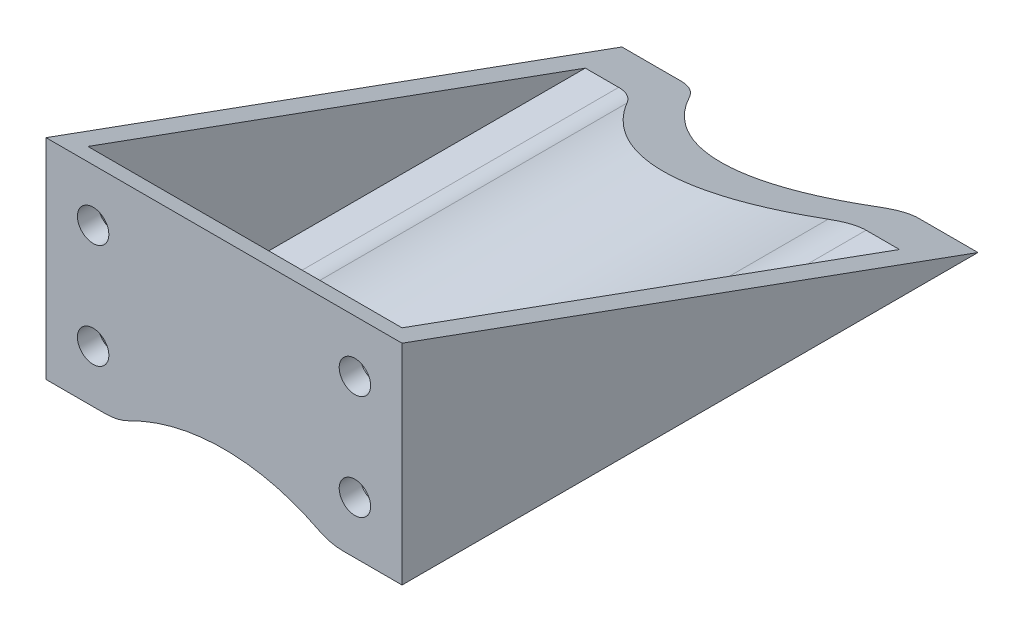
SolidWorks part; units mm, degrees
ref_plane "Alzado" through (0, 0, 0) normal (0, 0, 1) x (1, 0, 0)
ref_plane "Planta" through (0, 0, 0) normal (0, 1, 0) x (1, 0, 0)
ref_plane "Vista lateral" through (0, 0, 0) normal (1, 0, 0) x (0, 0, -1)
sketch "Croquis4" plane through (0, 0, 0) normal (1, 0, 0) x (0, 0, -1)
  line L0 (0, 0) -> (55, 0)
  line L1 (55, 0) -> (0, 20)
  line L2 (0, 20) -> (0, 0)
  dimension "D1" = 20
  dimension "D2" = 55
extrude "Saliente-Extruir3" add sketch "Croquis4" along normal blind 34
sketch "Croquis5" plane through (0, 0, 0) normal (0, 0, 1) x (1, 0, 0)
  line L0 (0, 0) -> (34, 20) construction
  line L2 (29.5, 5) -> (4.5, 5)
  line L3 (29.5, 5) -> (29.5, 15)
  line L4 (29.5, 15) -> (4.5, 15)
  line L5 (4.5, 5) -> (4.5, 15)
  line L6 (29.5, 5) -> (4.5, 15) construction
  line L7 (29.5, 15) -> (4.5, 5) construction
  circle A0 centre (4.5, 15) radius 1.5
  circle A1 centre (29.5, 15) radius 1.5
  circle A2 centre (29.5, 5) radius 1.5
  circle A3 centre (4.5, 5) radius 1.5
  point P4 (17, 10)
  dimension "D3" = 2
  dimension "D1" = 25
  dimension "D2" = 10
  dimension "D4" = 2
sketch "Croquis6" plane through (0, 0, 0) normal (0, 0, 1) x (1, 0, 0)
  line L0 (17, 0) -> (17, -17) construction
  line L1 (34, 0) -> (0, 0) construction
  circle A0 centre (17, -17) radius 19.75
  dimension "D1" = 39.5
  dimension "D2" = 17
extrude "Cortar-Extruir2" cut sketch "Croquis6" against normal through all
shell "Vaciado3" thickness 2 removed face at (17, 7.125, -35.4062)
extrude "Cortar-Extruir3" cut sketch "Croquis5" against normal blind 10 contours A0 | A1 | A2 | A3
fillet "Redondeo1" radius 5 2 edges at (6.947, 0, -27.5) (27.053, 0, -27.5)
fillet "Redondeo3" radius 5 2 edges at (27.586, 2, -25.75) (6.414, 2, -25.75)
